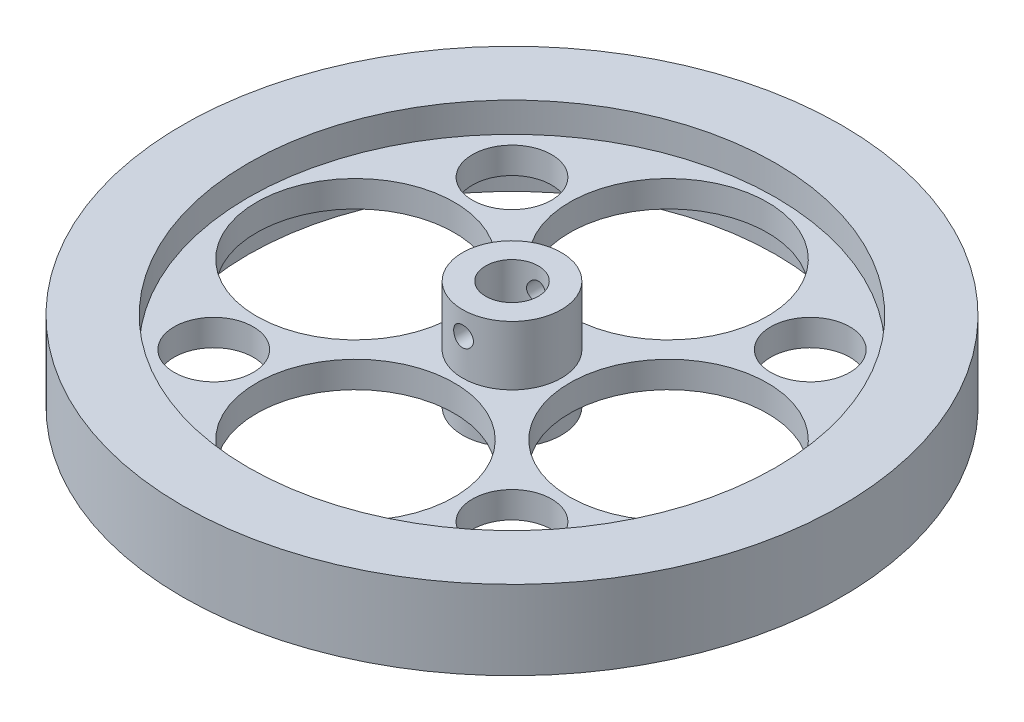
SolidWorks part; units mm, degrees
ref_plane "Front Plane" through (0, 0, 0) normal (0, 0, 1) x (1, 0, 0)
ref_plane "Top Plane" through (0, 0, 0) normal (0, 1, 0) x (1, 0, 0)
ref_plane "Right Plane" through (0, 0, 0) normal (1, 0, 0) x (0, 0, -1)
sketch "Sketch1" plane through (0, 0, 0) normal (0, 1, 0) x (1, 0, 0)
  circle A0 centre (0, 0) radius 50
  circle A1 centre (0, 0) radius 40
  circle A2 centre (0, 0) radius 7.5
  circle A3 centre (0, 0) radius 4
  circle A4 centre (0, 0) radius 1.5
extrude "Boss-Extrude1" add sketch "Sketch1" along normal blind 12 contours A0 A1 region at (-48.5858, 0, 0)
extrude "Boss-Extrude2" add sketch "Sketch1<4>" along normal blind 16.5 separate body contours A2 A3 region at (-7.2879, 0, 0)
sketch "Sketch1<4>" plane through (0, 0, 0) normal (0, 1, 0) x (1, 0, 0) same geometry as "Sketch1"
extrude "Boss-Extrude3" add sketch "Sketch1<5>" along normal blind 4 from offset 3.5 contours A1 A2 region at (-38.8686, 0, 0)
sketch "Sketch1<5>" plane through (0, 0, 0) normal (0, 1, 0) x (1, 0, 0) same geometry as "Sketch1"
sketch "Sketch2" plane through (0, 0, 0) normal (0, 1, 0) x (1, 0, 0)
  line L0 (0, 0) -> (0, 29.6201) construction
  line L1 (0, 0) -> (-22.6274, 22.6274) construction
  circle A0 centre (0, 0) radius 23.75 construction
  circle A1 centre (0, 23.75) radius 15
  circle A2 centre (23.75, 0) radius 15
  circle A3 centre (0, -23.75) radius 15
  circle A4 centre (-23.75, 0) radius 15
  circle A5 centre (0, 0) radius 32 construction
  circle A7 centre (-22.6274, 22.6274) radius 6
  circle A8 centre (22.6274, 22.6274) radius 6
  circle A9 centre (22.6274, -22.6274) radius 6
  circle A10 centre (-22.6274, -22.6274) radius 6
  point P14 (0, 0)
  point P25 (0, 0)
  dimension "D1" = 4
  dimension "D2" = 45
  dimension "D3" = 4
extrude "Cut-Extrude3" cut sketch "Sketch2" against normal through all and the other way through all contours A4 | A3 | A10 | A7 | A1 | A2 | A9 | A8 region at (0, 0, -23.75) region at (23.75, 0, 0) region at (0, 0, 23.75) region at (-23.75, 0, 0) region at (-22.6274, 0, -22.6274) region at (22.6274, 0, -22.6274) region at (22.6274, 0, 22.6274) region at (-22.6274, 0, 22.6274)
sketch "Sketch3" plane through (0, 0, 0) normal (0, 0, 1) x (1, 0, 0)
  line L0 (0, 16.5) -> (0, 13)
  line L1 (7.5, 16.5) -> (-7.5, 16.5) construction
  circle A0 centre (0, 13) radius 1.5
extrude "Cut-Extrude4" cut sketch "Sketch3" against normal blind 10 and the other way blind 10 contours A0 region at (-1.0307, 11.9693, 0)
